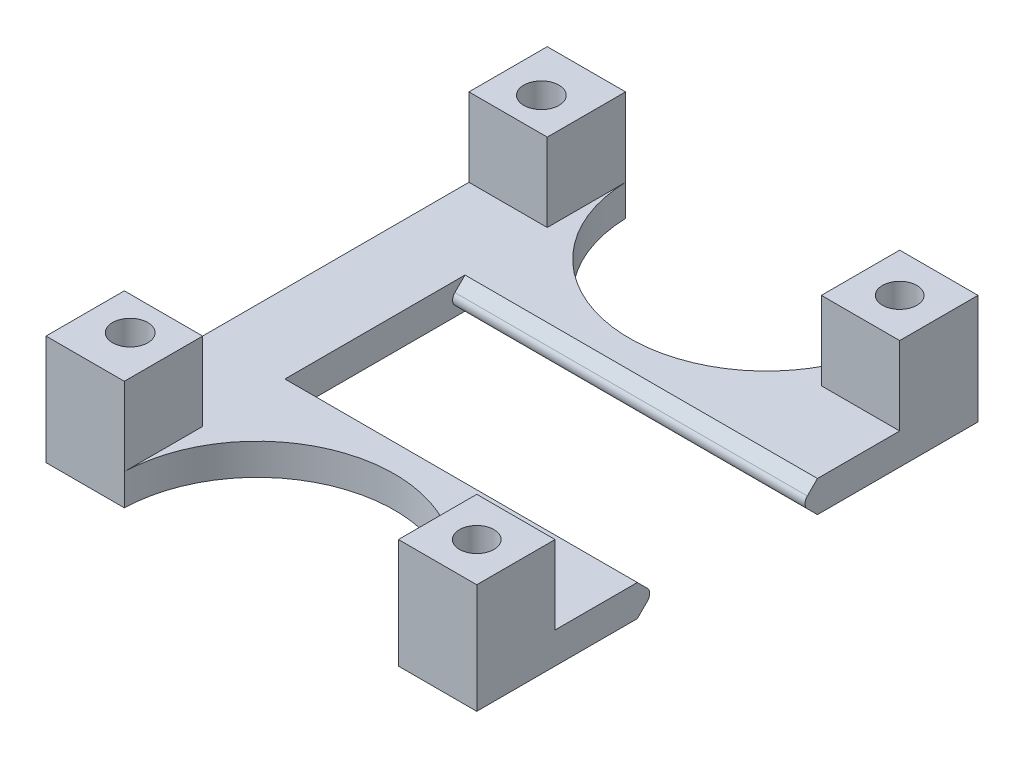
SolidWorks part; units mm, degrees
ref_plane "Front Plane" through (0, 0, 0) normal (0, 0, 1) x (1, 0, 0)
ref_plane "Top Plane" through (0, 0, 0) normal (0, 1, 0) x (1, 0, 0)
ref_plane "Right Plane" through (0, 0, 0) normal (1, 0, 0) x (0, 0, -1)
sketch "Sketch1" plane through (0, 0, 0) normal (0, 1, 0) x (1, 0, 0)
  line L0 (10, 10) -> (10, -10)
  line L2 (0, -20) -> (0, 20)
  line L4 (55, -20) -> (55, 20) construction
  line L5 (10, -10) -> (45, -10)
  line L6 (45, -10) -> (45, 10) construction
  line L7 (45, 10) -> (10, 10)
  line L8 (45, 10) -> (55, 10)
  line L11 (55, 10) -> (55, 20)
  line L13 (27.5, -20) -> (27.5, -10) construction
  line L14 (27.5, 10) -> (27.5, 20) construction
  line L16 (45, -10) -> (55, -10)
  line L17 (55, -20) -> (55, -10)
  line L18 (55, -20) -> (55, -32)
  line L19 (55, -32) -> (45, -32)
  line L21 (55, 20) -> (55, 32)
  line L22 (55, 32) -> (45, 32)
  line L24 (0, -20) -> (0, -32)
  line L27 (0, 20) -> (0, 32)
  line L30 (-55, 0) -> (55, 0) construction
  line L31 (0, 0) -> (55, 0) construction
  line L32 (10, -32) -> (0, -32)
  line L34 (10, 32) -> (0, 32)
  arc A26 (45, -32) -> (10, -32) centre (27.5, -32.5074) ccw
  arc A27 (45, 32) -> (10, 32) centre (27.5, 32.5074) cw
  circle A46 centre (50, 27) radius 2.2
  circle A47 centre (50, -27) radius 2.2
  circle A49 centre (5, -26.25) radius 2.2479 construction
  circle A50 centre (5, -26.25) radius 2.2479
  circle A51 centre (5, 26.25) radius 2.2479 construction
  circle A52 centre (5, 26.25) radius 2.2479
  point P30 (27.5, -15)
  point P35 (27.5, 15)
  point P36 (27.5, -10)
  point P39 (0, 0)
  dimension "D18" = 4.4
  dimension "D1" = 40
  dimension "D2" = 55
  dimension "D24" = 10
  dimension "D13" = 5
  dimension "D16" = 5
  dimension "D7" = 10
  dimension "D9" = 5
  dimension "D14" = 5
  dimension "D4" = 20
  dimension "D5" = 10
  dimension "D3" = 10
  dimension "D6" = 35
  dimension "D8" = 12
  dimension "D10" = 10
extrude "Extrude-Body" add sketch "Sketch1" along normal blind 4 contours L4 L2 A47 A46 L7 L6 L5 L0 | L19 L18 A47 | L22 L21 A46 | L27 | L24 region at (9.1561, 0, 0)
sketch "Sketch5" plane through (0, 4, 0) normal (0, 1, 0) x (1, 0, 0)
  line L6 (10, -32) -> (0, -32) construction
  line L9 (45, -22) -> (55, -22)
  line L21 (55, -22) -> (55, -32)
  line L23 (0, -32) -> (0, 32) construction
  line L34 (10, 32) -> (0, 32) construction
  line L36 (55, -32) -> (45, -32)
  line L37 (45, -32) -> (45, -22)
  line L38 (55, 22) -> (55, 32)
  line L39 (55, 32) -> (45, 32)
  line L41 (45, 32) -> (45, 22)
  line L42 (45, 22) -> (55, 22)
  line L43 (10, 22) -> (10, 32)
  line L44 (10, 32) -> (0, 32)
  line L46 (0, 32) -> (0, 22)
  line L47 (0, -32) -> (0, 32) construction
  line L48 (0, 22) -> (10, 22)
  line L49 (10, -22) -> (0, -22)
  line L50 (0, -22) -> (0, -32)
  line L51 (0, -32) -> (10, -32)
  line L52 (10, -32) -> (10, -22)
  circle A0 centre (50, 27) radius 2.2
  circle A3 centre (50, -27) radius 2.2
  circle A11 centre (50, 27) radius 2.2 construction
  circle A12 centre (50, -27) radius 2.2 construction
  circle A13 centre (5, 26.25) radius 2.2479 construction
  circle A14 centre (5, 26.25) radius 2.2479
  circle A15 centre (5, -26.25) radius 2.2479 construction
  circle A16 centre (5, -26.25) radius 2.2479
  dimension "D1" = 10
  dimension "D2" = 10
  dimension "D3" = 10
  dimension "D4" = 10
  dimension "D5" = 10
  dimension "D6" = 10
  dimension "D8" = 10
extrude "Extrude-Legs" add sketch "Sketch5" along normal blind 10
sketch "Sketch6" plane through (0, 4, 0) normal (0, 1, 0) x (1, 0, 0)
  line L0 (55, -10) -> (55, -22) construction
  line L1 (10, -10) -> (55, -10)
  line L2 (10, -10) -> (10, -9.5)
  line L3 (10, -9.5) -> (55, -9.5)
  line L4 (55, -10) -> (55, -9.5)
  line L5 (10, 10) -> (55, 10)
  line L6 (10, 10) -> (10, 9.5)
  line L7 (10, 9.5) -> (55, 9.5)
  line L8 (55, 10) -> (55, 9.5)
  line L9 (55, 10) -> (55, 22) construction
  dimension "D1" = 19
extrude "Boss-Extrude1" add sketch "Sketch6" against normal up to surface (4 mm away) up to face at (5, 0, -24.0021)
sketch "Sketch7" plane through (55, 0, 0) normal (1, 0, 0) x (0, 0, -1)
  line L0 (-10.2071, 2.7071) -> (-11.5, 4)
  line L1 (-9.5, 0) -> (-9.5, 4) construction
  line L2 (-9.5, 4) -> (-22, 4) construction
  line L3 (-10.2071, 1.2929) -> (-11.5, 0)
  line L4 (-9.5, 0) -> (-32, 0) construction
  line L5 (10.2071, 2.7071) -> (11.5, 4)
  line L6 (9.5, 0) -> (9.5, 4) construction
  line L7 (9.5, 4) -> (22, 4) construction
  line L8 (10.2071, 1.2929) -> (11.5, 0)
  line L9 (9.5, 0) -> (32, 0) construction
  line L10 (11.5, 4) -> (9.5, 4)
  line L11 (9.5, 0) -> (9.5, 4) construction
  line L12 (9.5, 4) -> (9.5, 0)
  line L13 (9.5, 0) -> (11.5, 0)
  line L14 (-11.5, 4) -> (-9.5, 4)
  line L15 (-9.5, 4) -> (-9.5, 0)
  line L16 (-9.5, 0) -> (-11.5, 0)
  line L17 (0, 0) -> (0, 8.2974) construction
  arc A0 (10.2071, 2.7071) -> (10.2071, 1.2929) centre (10.9142, 2) ccw
  arc A1 (-10.2071, 2.7071) -> (-10.2071, 1.2929) centre (-10.9142, 2) cw
  point P30 (11.5, 0)
  point P31 (11.5, 0)
  point P32 (9.5, 2)
  point P33 (0, 0)
  point P36 (9.5, 2)
  point P39 (-9.5, 2)
  dimension "D3" = 1
  dimension "D1" = 45
  dimension "D2" = 45
extrude "Cut-Extrude1" cut sketch "Sketch7" against normal up to surface (45 mm away) up to face at (10, 2, 0)
equation "\"boltdiameter\"=4.4"
equation "\"D18@Sketch1\"=\"boltdiameter\""
equation "\"boltfacediameter\"=7"
equation "\"insetNutFlat\"=8.4"
equation "\"screwInset\"=8.43"
equation "\"slotLength\"=80"
